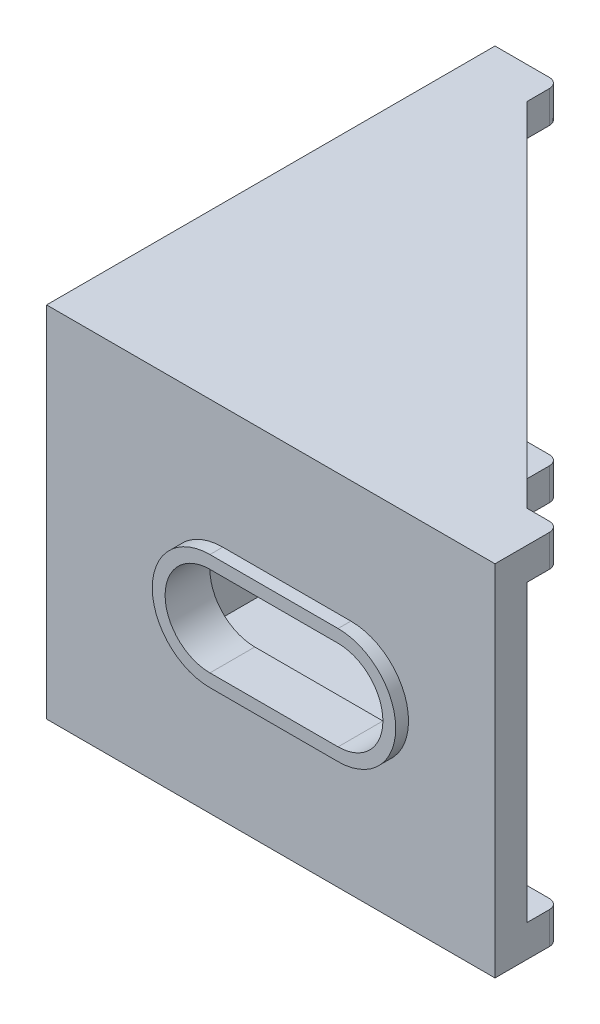
SolidWorks part; units mm, degrees
material "1060 Alloy"
ref_plane "Front Plane" through (0, 0, 0) normal (0, 0, 1) x (1, 0, 0)
ref_plane "Top Plane" through (0, 0, 0) normal (0, 1, 0) x (1, 0, 0)
ref_plane "Right Plane" through (0, 0, 0) normal (1, 0, 0) x (0, 0, -1)
sketch "Sketch1" plane through (0, 0, 0) normal (0, 1, 0) x (1, 0, 0)
  line L0 (0, 0) -> (0, 35)
  line L1 (0, 0) -> (35, 0)
  line L6 (2.5, 2.5) -> (35, 2.5)
  line L7 (2.5, 2.5) -> (2.5, 35)
  line L8 (0, 35) -> (2.5, 35)
  line L9 (35, 2.5) -> (35, 0)
  dimension "D2" = 35
  dimension "D3" = 35
  dimension "D1" = 2.5
extrude "Boss-Extrude1" add sketch "Sketch1" along normal blind 28
sketch "Sketch2" plane through (0, 28, 0) normal (0, 1, 0) x (1, 0, 0)
  line L0 (2.5, 35) -> (4.25, 35)
  line L1 (5, 34.25) -> (5, 32.5)
  line L2 (5, 32.5) -> (32.5, 5)
  line L3 (32.5, 5) -> (34.25, 5)
  line L4 (35, 4.25) -> (35, 2.5)
  line L5 (2.5, 2.5) -> (2.5, 35) construction
  line L6 (35, 2.5) -> (2.5, 2.5) construction
  line L7 (2.5, 2.5) -> (2.5, 35)
  line L8 (35, 2.5) -> (2.5, 2.5)
  arc A0 (34.25, 5) -> (35, 4.25) centre (34.25, 4.25) cw
  arc A1 (4.25, 35) -> (5, 34.25) centre (4.25, 34.25) cw
  point P12 (35, 5)
  dimension "D5" = 0.75
  dimension "D1" = 2.5
  dimension "D2" = 45
  dimension "D3" = 2.5
  dimension "D4" = 2.5
extrude "Boss-Extrude2" add sketch "Sketch2" against normal blind 2.5
extrude "Boss-Extrude3" add sketch "Sketch2<2>" along normal blind 2.5 from surface starting at face at (12.5, 0, -12.5)
sketch "Sketch2<2>" plane through (0, 28, 0) normal (0, 1, 0) x (1, 0, 0) same geometry as "Sketch2"
sketch "Sketch3" plane through (0, 0, -2.5) normal (0, 0, -1) x (-1, 0, 0)
  line L0 (-23.75, 14) -> (-13.75, 14) construction
  line L1 (-23.75, 17.5) -> (-13.75, 17.5)
  line L2 (-23.75, 10.5) -> (-13.75, 10.5)
  line L3 (-32.5, 25.5) -> (-5, 25.5) construction
  line L4 (-5, 2.5) -> (-32.5, 2.5) construction
  line L5 (-18.75, 2.5) -> (-18.75, 25.5) construction
  line L6 (-35, 2.5) -> (-2.5, 2.5) construction
  line L7 (-2.5, 25.5) -> (-2.5, 2.5) construction
  arc A0 (-23.75, 17.5) -> (-23.75, 10.5) centre (-23.75, 14) ccw
  arc A1 (-13.75, 10.5) -> (-13.75, 17.5) centre (-13.75, 14) ccw
  point P2 (-18.75, 14)
  point P15 (-10.25, 14)
  dimension "D1" = 7
  dimension "D2" = 10
  dimension "D3" = 7.75
extrude "Cut-Extrude1" cut sketch "Sketch3" against normal blind 2.5
sketch "Sketch4" plane through (2.5, 0, 0) normal (1, 0, 0) x (0, 0, -1)
  line L0 (13.75, 14) -> (23.75, 14) construction
  line L1 (13.75, 17.5) -> (23.75, 17.5)
  line L2 (13.75, 10.5) -> (23.75, 10.5)
  line L3 (35, 25.5) -> (2.5, 25.5) construction
  line L4 (2.5, 2.5) -> (35, 2.5) construction
  line L5 (18.75, 2.5) -> (18.75, 25.5) construction
  line L6 (5, 25.5) -> (32.5, 25.5) construction
  arc A0 (13.75, 17.5) -> (13.75, 10.5) centre (13.75, 14) ccw
  arc A1 (23.75, 10.5) -> (23.75, 17.5) centre (23.75, 14) ccw
  point P2 (18.75, 14)
  dimension "D1" = 10
  dimension "D2" = 7
extrude "Cut-Extrude2" cut sketch "Sketch4" against normal blind 2.5
sketch "Sketch5" plane through (0, 0, 0) normal (0, 0, 1) x (1, 0, 0)
  line L0 (13.75, 17.5) -> (23.75, 17.5) construction
  line L1 (23.75, 10.5) -> (13.75, 10.5) construction
  line L2 (13.75, 17.5) -> (23.75, 17.5)
  line L3 (23.75, 10.5) -> (13.75, 10.5)
  line L4 (13.75, 18.5) -> (23.75, 18.5)
  line L5 (23.75, 9.5) -> (13.75, 9.5)
  arc A0 (13.75, 17.5) -> (13.75, 10.5) centre (13.75, 14) ccw construction
  arc A1 (23.75, 10.5) -> (23.75, 17.5) centre (23.75, 14) ccw construction
  arc A2 (13.75, 17.5) -> (13.75, 10.5) centre (13.75, 14) ccw
  arc A3 (23.75, 10.5) -> (23.75, 17.5) centre (23.75, 14) ccw
  arc A4 (23.75, 9.5) -> (23.75, 18.5) centre (23.75, 14) ccw
  arc A5 (13.75, 18.5) -> (13.75, 9.5) centre (13.75, 14) ccw
  dimension "D1" = 1
extrude "Boss-Extrude4" add sketch "Sketch5" along normal blind 1
sketch "Sketch6" plane through (0, 0, 0) normal (-1, 0, 0) x (0, 0, 1)
  line L0 (-13.75, 10.5) -> (-23.75, 10.5) construction
  line L1 (-23.75, 17.5) -> (-13.75, 17.5) construction
  line L2 (-13.75, 10.5) -> (-23.75, 10.5)
  line L3 (-23.75, 17.5) -> (-13.75, 17.5)
  line L4 (-23.75, 18.5) -> (-13.75, 18.5)
  line L5 (-13.75, 9.5) -> (-23.75, 9.5)
  arc A0 (-13.75, 10.5) -> (-13.75, 17.5) centre (-13.75, 14) ccw construction
  arc A1 (-13.75, 10.5) -> (-13.75, 17.5) centre (-13.75, 14) ccw
  arc A2 (-23.75, 17.5) -> (-23.75, 10.5) centre (-23.75, 14) ccw construction
  arc A3 (-23.75, 17.5) -> (-23.75, 10.5) centre (-23.75, 14) ccw
  arc A4 (-13.75, 9.5) -> (-13.75, 18.5) centre (-13.75, 14) ccw
  arc A5 (-23.75, 18.5) -> (-23.75, 9.5) centre (-23.75, 14) ccw
  dimension "D1" = 1
extrude "Boss-Extrude5" [suppressed] add sketch "Sketch6" along normal blind 1
